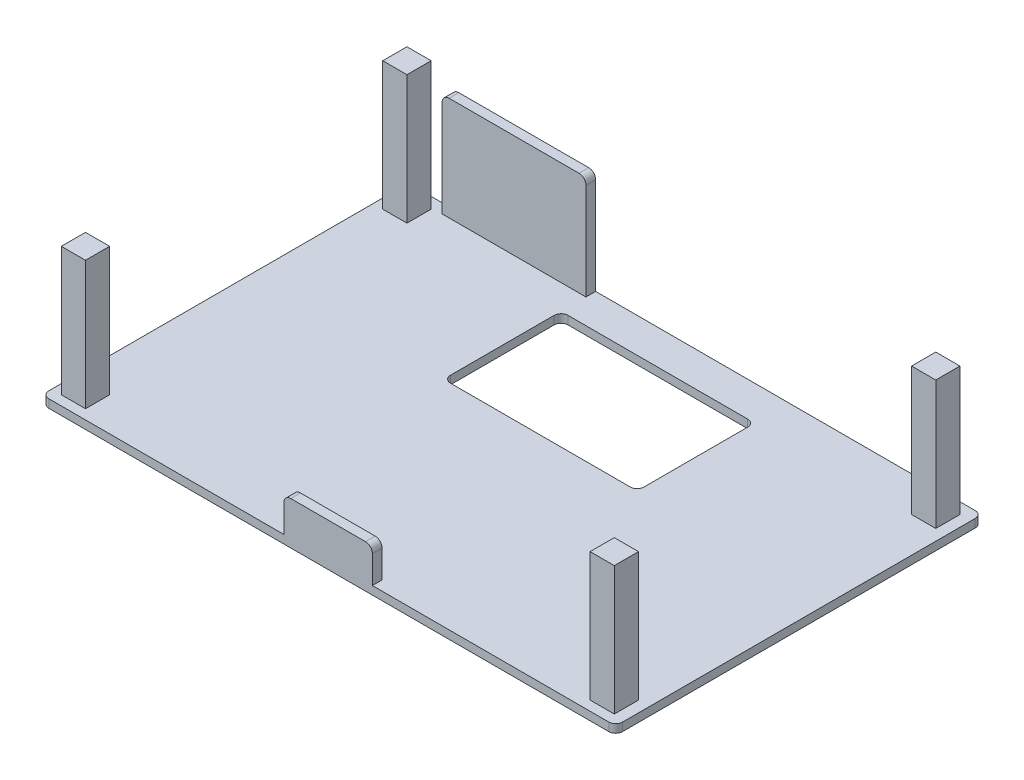
SolidWorks part; units mm, degrees
ref_plane "前视基准面" through (0, 0, 0) normal (0, 0, 1) x (1, 0, 0)
ref_plane "上视基准面" through (0, 0, 0) normal (0, 1, 0) x (1, 0, 0)
ref_plane "右视基准面" through (0, 0, 0) normal (1, 0, 0) x (0, 0, -1)
sketch "草图1" plane through (0, 0, 0) normal (0, 1, 0) x (1, 0, 0)
  line L1 (0, 0) -> (80, 0)
  line L2 (0, 0) -> (0, 50)
  line L3 (0, 50) -> (80, 50)
  line L4 (80, 0) -> (80, 50)
  line L5 (-1.4, -1.4) -> (81.6, -1.4)
  line L6 (-1.4, -1.4) -> (-1.4, 51.6)
  line L7 (-1.4, 51.6) -> (81.6, 51.6)
  line L8 (81.6, -1.4) -> (81.6, 51.6)
  line L9 (0, 50) -> (3.5, 50)
  line L10 (0, 50) -> (0, 46.5)
  line L11 (0, 46.5) -> (3.5, 46.5)
  line L12 (3.5, 50) -> (3.5, 46.5)
  line L13 (0, 0) -> (3.5, 0)
  line L14 (0, 0) -> (0, 3.5)
  line L15 (0, 3.5) -> (3.5, 3.5)
  line L16 (3.5, 0) -> (3.5, 3.5)
  line L17 (80, 0) -> (76.5, 0)
  line L18 (80, 0) -> (80, 3.5)
  line L19 (80, 3.5) -> (76.5, 3.5)
  line L20 (76.5, 0) -> (76.5, 3.5)
  line L21 (80, 50) -> (76.5, 50)
  line L22 (80, 50) -> (80, 46.5)
  line L23 (80, 46.5) -> (76.5, 46.5)
  line L24 (76.5, 50) -> (76.5, 46.5)
  dimension "D1" = 80
  dimension "D2" = 50
  dimension "D3" = 83
  dimension "D4" = 53
  dimension "D5" = 1.4
  dimension "D6" = 1.4
  dimension "D7" = 3.5
  dimension "D8" = 3.5
  dimension "D9" = 3.5
  dimension "D10" = 3.5
  dimension "D11" = 3.5
  dimension "D12" = 3.5
  dimension "D13" = 3.5
  dimension "D14" = 3.5
extrude "凸台-拉伸1" add sketch "草图1" along normal blind 1.2 contours L5 L8 L7 L6 L4 L1 L2 L3 region at (-0.4152, 0, -25.1)
extrude "凸台-拉伸2" add sketch "草图1<4>" along normal blind 19.8 contours L12 L3 L2 L11 | L1 L16 L15 L2 | L3 L24 L23 L4 | L20 L1 L4 L19 region at (1.75, 0, -1.75) region at (78.25, 0, -1.75) region at (1.75, 0, -48.25) region at (78.25, 0, -48.25)
sketch "草图1<4>" plane through (0, 0, 0) normal (0, 1, 0) x (1, 0, 0) same geometry as "草图1"
extrude "凸台-拉伸3" add sketch "草图1<5>" along normal blind 1.2 contours L24 L3 L12 L11 L2 L15 L16 L1 L20 L19 L4 L23 region at (40, 0, -25)
sketch "草图1<5>" plane through (0, 0, 0) normal (0, 1, 0) x (1, 0, 0) same geometry as "草图1"
sketch "草图3" plane through (0, 1.2, 0) normal (0, 1, 0) x (1, 0, 0)
  line L0 (-1.4, -1.4) -> (-1.4, 51.6) construction
  line L1 (4.9, 50.2) -> (25.7, 50.2)
  line L2 (4.9, 50.2) -> (4.9, 51.6)
  line L3 (4.9, 51.6) -> (25.7, 51.6)
  line L4 (25.7, 50.2) -> (25.7, 51.6)
  line L5 (-1.4, 51.6) -> (81.6, 51.6) construction
  dimension "D1" = 6.3
  dimension "D2" = 20.8
  dimension "D3" = 0
  dimension "D4" = 1.4
extrude "凸台-拉伸4" add sketch "草图3" along normal blind 15
sketch "草图4" plane through (0, 1.2, 0) normal (0, 1, 0) x (1, 0, 0)
  line L0 (-1.4, -1.4) -> (81.6, -1.4) construction
  line L1 (33.6, -1.4) -> (46.4, -1.4)
  line L2 (33.6, -1.4) -> (33.6, 0)
  line L3 (33.6, 0) -> (46.4, 0)
  line L4 (46.4, -1.4) -> (46.4, 0)
  line L5 (81.6, -1.4) -> (81.6, 51.6) construction
  dimension "D1" = 35.2
  dimension "D2" = 12.8
  dimension "D3" = 1.4
extrude "凸台-拉伸5" add sketch "草图4" along normal blind 5
sketch "草图5" plane through (0, 1.2, 0) normal (0, 1, 0) x (1, 0, 0)
  line L0 (25.7, 50.2) -> (25.7, 51.6) construction
  line L1 (25.7, 46.6) -> (53.7, 46.6)
  line L2 (25.7, 46.6) -> (25.7, 29.6)
  line L3 (25.7, 29.6) -> (53.7, 29.6)
  line L4 (53.7, 46.6) -> (53.7, 29.6)
  line L5 (25.7, 51.6) -> (81.6, 51.6) construction
  dimension "D1" = 0
  dimension "D2" = 5
  dimension "D3" = 22
  dimension "D4" = 28
extrude "切除-拉伸1" cut sketch "草图5" against normal blind 5
fillet "圆角2" radius 1 8 edges at (81.6, 0.6, -51.6) (81.6, 0.6, 1.4) (-1.4, 0.6, -51.6) (-1.4, 0.6, 1.4) (53.7, 0.6, -29.6) (25.7, 0.6, -29.6) (25.7, 0.6, -46.6) (53.7, 0.6, -46.6)
fillet "圆角3" radius 1 2 edges at (4.9, 16.2, -50.9) (25.7, 16.2, -50.9)
fillet "圆角4" radius 1 2 edges at (46.4, 6.2, 0.7) (33.6, 6.2, 0.7)
